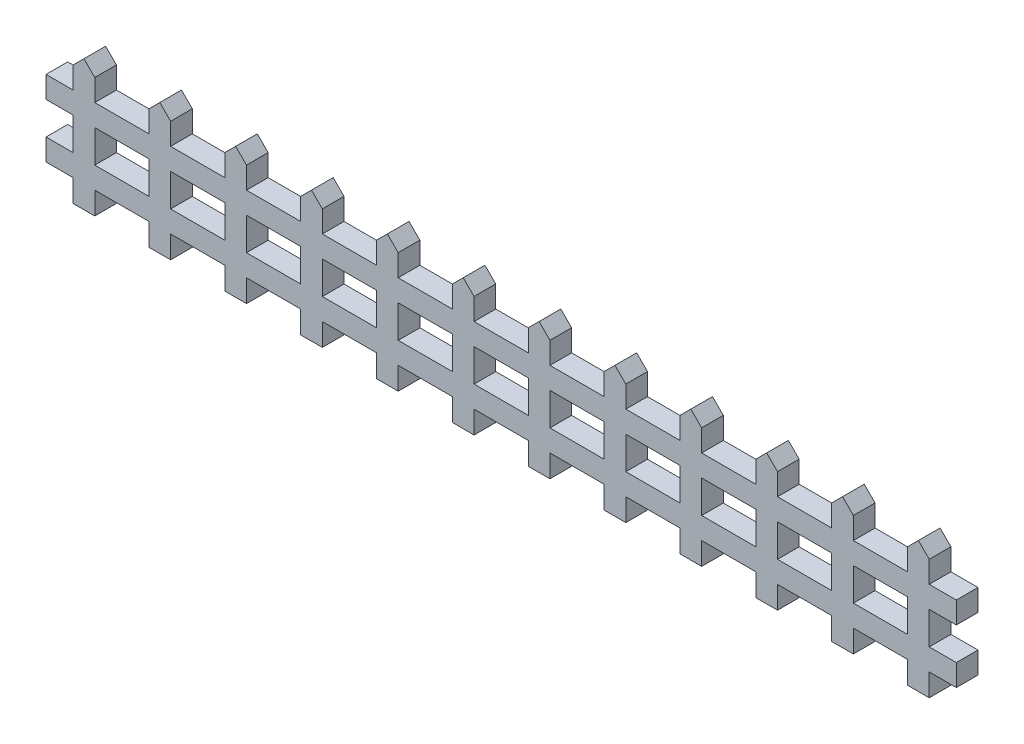
SolidWorks part; units mm, degrees
ref_plane "Front Plane" through (0, 0, 0) normal (1, 0, 0) x (0, 1, 0)
ref_plane "Top Plane" through (0, 0, 0) normal (0, 0, 1) x (0, 1, 0)
ref_plane "Right Plane" through (0, 0, 0) normal (0, 1, 0) x (-1, 0, 0)
sketch "Sketch1" plane through (0, 0, 0) normal (0, 0, 1) x (0, 1, 0)
  line L0 (-105, 74) -> (105, -74) construction
  line L1 (-105, 74) -> (105, 74) construction
  line L2 (-105, 74) -> (-105, -74) construction
  line L3 (-105, -74) -> (105, -74) construction
  line L4 (105, 74) -> (105, 63.1122) construction
  line L5 (84.9915, 53.1122) -> (82.9915, 53.1122)
  line L6 (100.9915, 67.1122) -> (98.9915, 67.1122)
  line L8 (100.9915, 63.1122) -> (98.9915, 63.1122)
  line L10 (94.9915, 72.1122) -> (98.9915, 72.1122)
  line L11 (94.9915, 72.1122) -> (94.9915, 67.1122)
  line L12 (94.9915, 44.1122) -> (98.9915, 44.1122)
  line L13 (98.9915, 72.1122) -> (98.9915, 67.1122)
  line L14 (88.9915, 72.1122) -> (84.9915, 72.1122)
  line L15 (88.9915, 72.1122) -> (88.9915, 67.1122)
  line L16 (88.9915, 44.1122) -> (84.9915, 44.1122)
  line L17 (84.9915, 72.1122) -> (84.9915, 67.1122)
  line L18 (100.9915, 53.1122) -> (98.9915, 53.1122)
  line L20 (100.9915, 49.1122) -> (98.9915, 49.1122)
  line L22 (84.9915, 49.1122) -> (82.9915, 49.1122)
  line L23 (88.9915, 49.1122) -> (88.9915, 44.1122)
  line L24 (98.9915, 49.1122) -> (98.9915, 44.1122)
  line L25 (94.9915, 49.1122) -> (94.9915, 44.1122)
  line L26 (84.9915, 49.1122) -> (84.9915, 44.1122)
  line L27 (94.9915, 53.1122) -> (88.9915, 53.1122)
  line L28 (94.9915, 63.1122) -> (88.9915, 63.1122)
  line L29 (94.9915, 63.1122) -> (94.9915, 53.1122)
  line L30 (98.9915, 63.1122) -> (98.9915, 53.1122)
  line L31 (88.9915, 63.1122) -> (88.9915, 53.1122)
  line L32 (84.9915, 63.1122) -> (84.9915, 53.1122)
  line L33 (84.9915, 63.1122) -> (82.9915, 63.1122)
  line L34 (84.9915, 67.1122) -> (82.9915, 67.1122)
  line L35 (94.9915, 67.1122) -> (88.9915, 67.1122)
  line L36 (94.9915, 49.1122) -> (88.9915, 49.1122)
  line L37 (105, 53.1122) -> (105, 49.1122)
  line L38 (100.9915, 67.1122) -> (105, 67.1122)
  line L40 (100.9915, 49.1122) -> (105, 49.1122)
  line L41 (105, 67.1122) -> (105, 63.1122)
  line L42 (82.9915, 67.1122) -> (80.8574, 67.1122)
  line L44 (82.9915, 49.1122) -> (80.8574, 49.1122)
  line L45 (80.8574, 67.1122) -> (80.8574, 63.1122)
  line L46 (82.9915, 63.1122) -> (80.8574, 63.1122)
  line L48 (82.9915, 53.1122) -> (80.8574, 53.1122)
  line L50 (100.9915, 53.1122) -> (105, 53.1122)
  line L52 (100.9915, 63.1122) -> (105, 63.1122)
  line L54 (105, 53.1122) -> (105, -74) construction
  line L56 (80.8574, 53.1122) -> (80.8574, 49.1122)
  dimension "D1" = 210
  dimension "D2" = 148
  dimension "D3" = 10
  dimension "D4" = 4
  dimension "D5" = 5
  dimension "D6" = 6
  dimension "D7" = 4
extrude "Boss-Extrude1" add sketch "Sketch1" along normal blind 4
chamfer "Chamfer1" distance 2 angle 45 4 edges at (-49.1122, 105, 2) (-53.1122, 105, 2) (-63.1122, 105, 2) (-67.1122, 105, 2)
pattern_linear "LPattern1" count 6 spacing 28 along (1, 0, 0) of "Chamfer1", "Boss-Extrude1"
